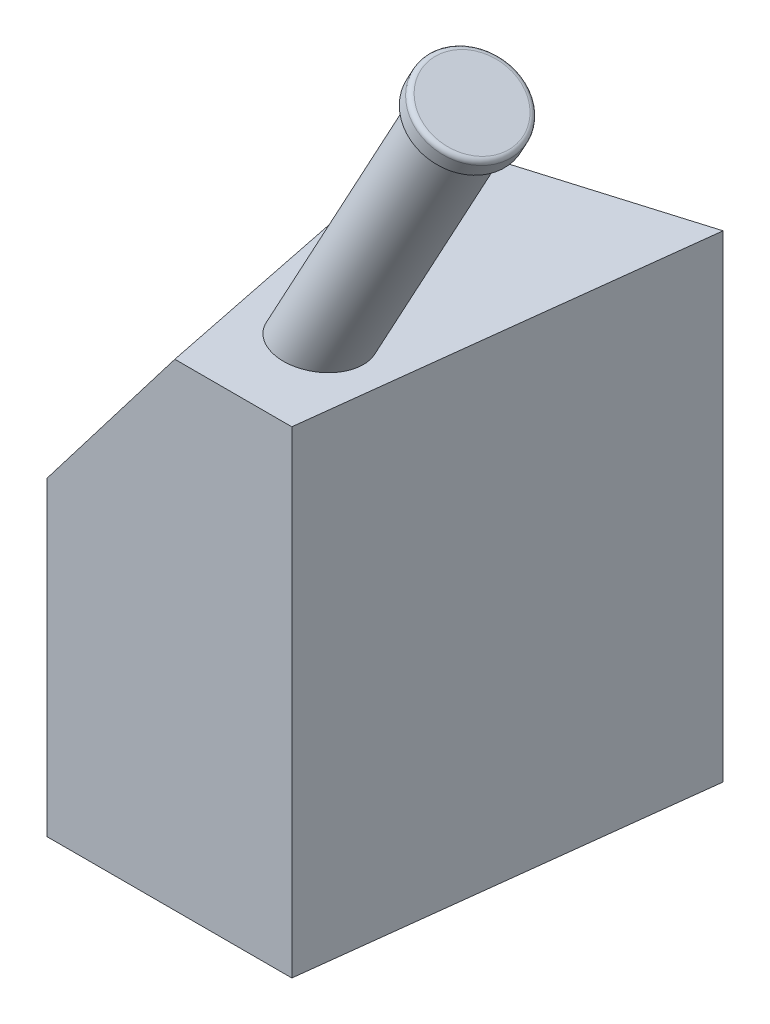
SolidWorks part; units mm, degrees
ref_plane "Front Plane" through (0, 0, 0) normal (0, 0, 1) x (1, 0, 0)
ref_plane "Top Plane" through (0, 0, 0) normal (0, 1, 0) x (1, 0, 0)
ref_plane "Right Plane" through (0, 0, 0) normal (1, 0, 0) x (0, 0, -1)
sketch "Sketch2" plane through (0, 0, 0) normal (0, 1, 0) x (1, 0, 0)
  line L0 (0, 0) -> (130.302, 0)
  line L1 (130.302, 0) -> (154.7294, 205.0521)
  line L2 (154.7294, 205.0521) -> (-52.1239, 143.2092)
  line L3 (-52.1239, 143.2092) -> (0, 0)
  dimension "D1" = 130.302
  dimension "D2" = 206.502
  dimension "D3" = 215.9
extrude "Boss-Extrude1" add sketch "Sketch2" along normal blind 254
ref_plane "Plane3" through (141.3327, 246.5263, 16.8366) normal (0.4965, 0.866, 0.0591) x (0.1183, 0, -0.993)
sketch "Sketch16" plane through (141.3327, 246.5263, 16.8366) normal (0.4965, 0.866, 0.0591) x (0.1183, 0, -0.993)
  circle A0 centre (59.5393, 48.3894) radius 20.3962
  dimension "D1" = 40.7924
extrude "Boss-Extrude2" add sketch "Sketch16" along normal blind 165.1 and the other way blind 50.8
sketch "Sketch17" plane through (223.3031, 389.5071, 26.6015) normal (0.4965, 0.866, 0.0591) x (0.868, -0.4953, -0.0338)
  circle A2 centre (-39.8244, 65.578) radius 25.4762
  circle A3 centre (-39.8244, 65.578) radius 25.4762
  dimension "D1" = 5.08
extrude "Boss-Extrude3" add sketch "Sketch17" against normal blind 10.16
fillet "Fillet1" radius 2.54 2 edges at (165.9949, 415.0472, -38.0778) (166.6321, 426.3726, -37.4768)
sketch "Sketch19" plane through (0, 0, 0) normal (0, 0, 1) x (1, 0, 0)
  line L0 (0, 254) -> (130.302, 254) construction
  line L1 (0, 254) -> (0, 0) construction
  point P0 (68.072, 254)
  point P1 (0, 165.1)
  dimension "D1" = 62.23
  dimension "D2" = 165.1
sketch "Sketch33" plane through (-43.5791, 0, -145.7638) normal (-0.2864, 0, -0.9581) x (-0.9581, 0, 0.2864)
  line L0 (8.9185, 254) -> (8.9185, 0) construction
  line L1 (-206.9815, 254) -> (8.9185, 254) construction
  point P0 (8.9185, 96.52)
  point P1 (-92.6815, 254)
  point P4 (0, 0)
  dimension "D1" = 114.3
  dimension "D2" = 96.52
ref_plane "Plane6" through (-74.2356, 46.7436, 4.635) normal (-0.845, 0.5321, 0.0528) x (0.0446, -0.0281, 0.9986)
sketch "Sketch35" plane through (-74.2356, 46.7436, 4.635) normal (-0.845, 0.5321, 0.0528) x (0.0446, -0.0281, 0.9986)
  line L0 (-177.1935, 239.0338) -> (49822.8065, 239.0338) construction
  point P3 (-117.5035, 239.0338)
  point P4 (0, 0)
  point P5 (0, 0)
  point P6 (0, 0)
  point P7 (0, 0)
  point P8 (0, 0)
  dimension "D1" = 59.69
sketch "Sketch37" plane through (-74.2356, 46.7436, 4.635) normal (-0.845, 0.5321, 0.0528) x (0.0446, -0.0281, 0.9986)
  line L0 (-177.1935, 239.0338) -> (-117.5035, 239.0338)
  line L1 (-117.5035, 239.0338) -> (-4.6414, 139.7108)
  line L2 (-4.6414, 139.7108) -> (-148.0503, 53.9036)
  line L3 (-148.0503, 53.9036) -> (-177.1935, 239.0338)
extrude "Cut-Extrude5" cut sketch "Sketch37" along normal through all
shell "Shell2" [suppressed] thickness 2.54
ref_plane "Plane8" through (-77.6744, 59.4764, 15.7733) normal (0.7838, -0.6002, -0.1592) x (-0.1264, 0.0968, -0.9873)
sketch "Sketch44" plane through (-77.6744, 59.4764, 15.7733) normal (0.7838, -0.6002, -0.1592) x (-0.1264, 0.0968, -0.9873)
  line L0 (129.9689, 229.1597) -> (15.977, 243.0534)
  line L1 (15.977, 243.0534) -> (15.977, 131.0847)
  line L2 (15.977, 131.0847) -> (129.9689, 229.1597)
extrude "Cut-Extrude14" cut sketch "Sketch44" against normal through all
sketch "Sketch46" plane through (0, 254, 0) normal (0, 1, 0) x (1, 0, 0)
  line L0 (45.2188, 172.3117) -> (45.2188, 112.5385)
  point P0 (45.2188, 112.5385)
  point P5 (0, 0)
sketch "Sketch54" plane through (48.3241, 47.921, 57.2723) normal (0.5433, 0.5388, 0.6439) x (0.8395, -0.3486, -0.4167)
  line L0 (-57.5596, 126.622) -> (-3.6988, 267.021)
  line L1 (-57.5596, 126.622) -> (-143.2464, 159.4938)
  line L2 (-3.6988, 267.021) -> (-89.3856, 299.8928)
  line L3 (-143.2464, 159.4938) -> (-89.3856, 299.8928)
extrude "Cut-Extrude16" cut sketch "Sketch54" against normal through all
sketch "Bend-Lines3" plane through (0, 0, 0) normal (0, 1, 0) x (1, 0, 0)
sketch "Bounding-Box3" plane through (0, 0, 0) normal (0, 1, 0) x (1, 0, 0)
